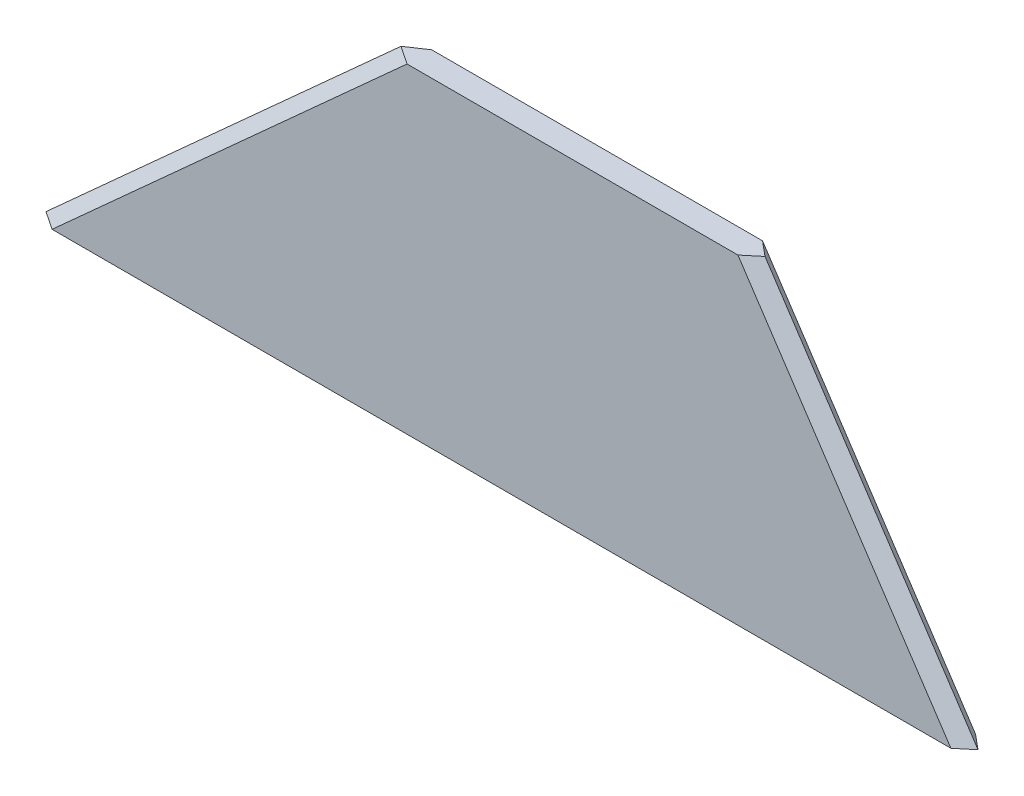
SolidWorks part; units mm, degrees
material "E-Glass Fiber"
ref_plane "Front Plane" through (0, 0, 0) normal (0, 0, 1) x (1, 0, 0)
ref_plane "Top Plane" through (0, 0, 0) normal (0, 1, 0) x (1, 0, 0)
ref_plane "Right Plane" through (0, 0, 0) normal (1, 0, 0) x (0, 0, -1)
sketch "Sketch1" plane through (0, 0, 0) normal (0, 0, 1) x (1, 0, 0)
  line L0 (0, 0) -> (203.2, 0)
  line L1 (203.2, 0) -> (157.48, 68.834)
  line L2 (157.48, 68.834) -> (76.2, 68.834)
  line L3 (76.2, 68.834) -> (0, 0)
  dimension "D1" = 203.2
  dimension "D2" = 81.28
  dimension "D3" = 76.2
  dimension "D4" = 68.834
extrude "Boss-Extrude1" add sketch "Sketch1" along normal blind 5.2832
chamfer "Chamfer1" distance 3.81 angle 45 4 edges at (180.34, 34.417, 5.2832) (180.34, 34.417, 0) (38.1, 34.417, 5.2832) (38.1, 34.417, 0)
